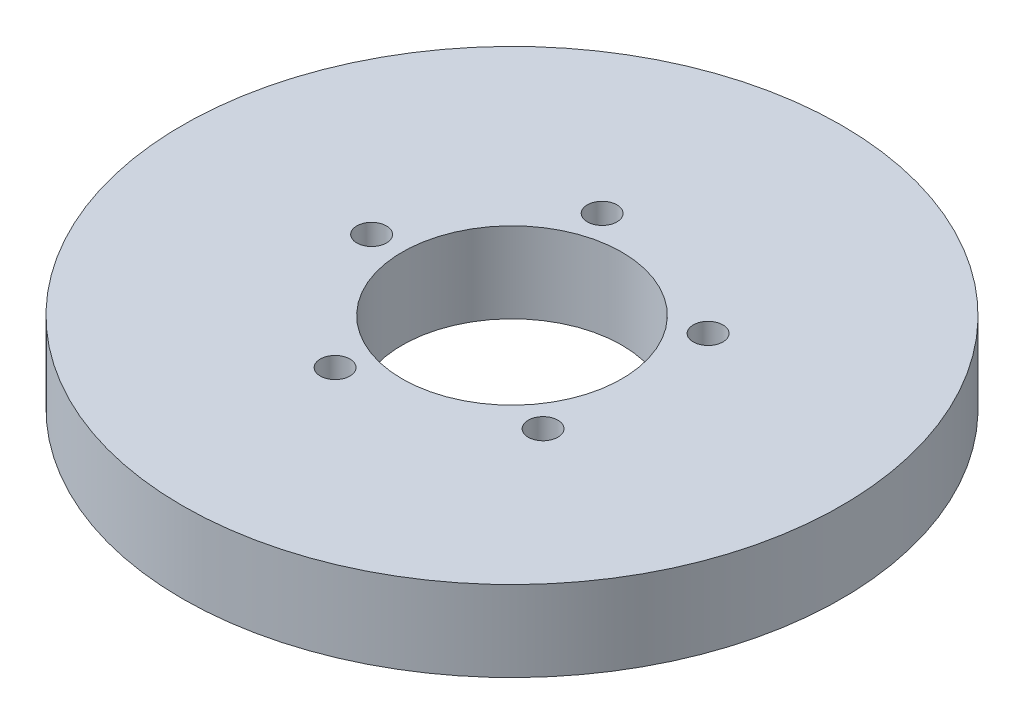
SolidWorks part; units mm, degrees
ref_plane "Front Plane" through (0, 0, 0) normal (0, 0, 1) x (1, 0, 0)
ref_plane "Top Plane" through (0, 0, 0) normal (0, 1, 0) x (1, 0, 0)
ref_plane "Right Plane" through (0, 0, 0) normal (1, 0, 0) x (0, 0, -1)
sketch "Sketch1" plane through (0, 0, 0) normal (0, 1, 0) x (1, 0, 0)
  circle A0 centre (0, 0) radius 45
  dimension "FLANGE_OD" = 90
extrude "Boss-Extrude1" add sketch "Sketch1" along normal blind 11
sketch "Sketch2" plane through (0, 0, 0) normal (0, 1, 0) x (1, 0, 0)
  circle A0 centre (0, 0) radius 15
  dimension "BORE_D" = 30
extrude "Cut-Extrude1" cut sketch "Sketch2" along normal through all
sketch "Sketch3" plane through (0, 11, 0) normal (0, 1, 0) x (1, 0, 0)
  circle A0 centre (0, 0) radius 19.1688 construction
  circle A1 centre (-19.1688, 0) radius 2.0238
  dimension "BOLT_D" = 4.0476
  dimension "BOLT_PCD" = 38.3376
extrude "Cut-Extrude2" cut sketch "Sketch3" against normal blind 8.7422
pattern_circular "CirPattern1" count 5 over 360 about axis through (0, 0, 0) along (0, 1, 0) of "Cut-Extrude2"
